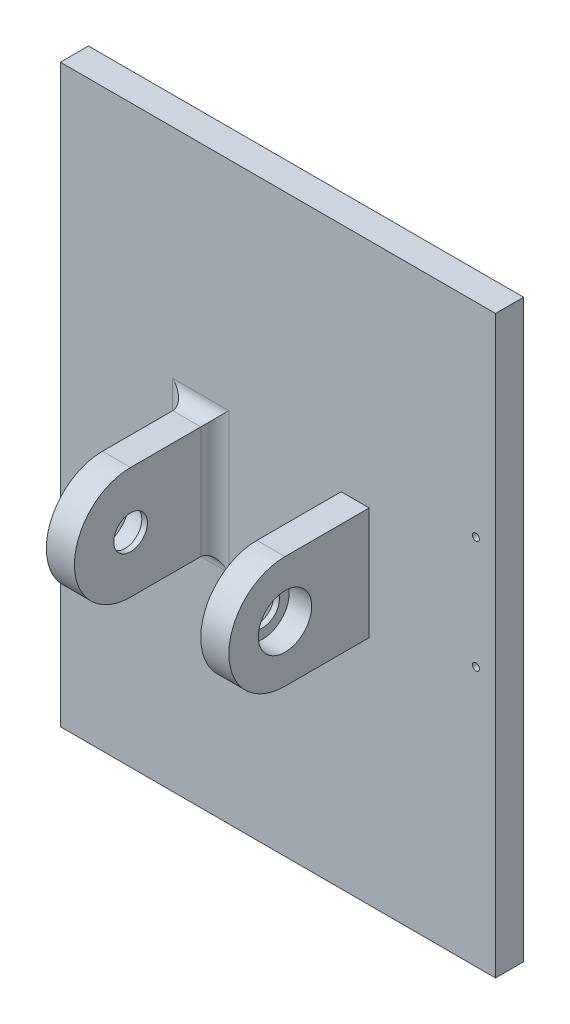
SolidWorks part; units mm, degrees
ref_plane "正面" through (0, 0, 0) normal (0, 0, 1) x (1, 0, 0)
ref_plane "平面" through (0, 0, 0) normal (0, 1, 0) x (1, 0, 0)
ref_plane "右側面" through (0, 0, 0) normal (1, 0, 0) x (0, 0, -1)
sketch "ｽｹｯﾁ2" plane through (0, 0, 0) normal (0, 0, 1) x (1, 0, 0)
  line L1 (-77.5, 102.5) -> (77.5, 102.5)
  line L2 (-77.5, 102.5) -> (-77.5, -102.5)
  line L3 (-77.5, -102.5) -> (77.5, -102.5)
  line L4 (77.5, 102.5) -> (77.5, -102.5)
  line L5 (-77.5, 102.5) -> (77.5, -102.5) construction
  line L6 (-77.5, -102.5) -> (77.5, 102.5) construction
  point P0 (0, 0)
  dimension "D1" = 155
  dimension "D2" = 205
extrude "ﾎﾞｽ - 押し出し1" add sketch "ｽｹｯﾁ2" along normal blind 10
sketch "ｽｹｯﾁ3" plane through (0, 0, 0) normal (0, 0, 1) x (1, 0, 0)
  line L0 (-32.5, 20) -> (-32.5, -20)
  line L1 (-32.5, -20) -> (-22.5, -20)
  line L2 (-22.5, -20) -> (-22.5, 20)
  line L3 (-22.5, 20) -> (-32.5, 20)
  dimension "D1" = 10
  dimension "D2" = 20
  dimension "D3" = 20
  dimension "D4" = 22.5
extrude "ﾎﾞｽ - 押し出し2" add sketch "ｽｹｯﾁ3" along normal blind 40
ref_plane "平面1" through (-32.5, 0, 0) normal (-1, 0, 0) x (0, 0, 1)
sketch "ｽｹｯﾁ4" plane through (-32.5, 0, 0) normal (-1, 0, 0) x (0, 0, 1)
  line L0 (40, 20) -> (40, -20) construction
  circle A0 centre (40, 0) radius 20
extrude "ﾎﾞｽ - 押し出し3" add sketch "ｽｹｯﾁ4" against normal blind 10
sketch "ｽｹｯﾁ5" plane through (-32.5, 0, 0) normal (-1, 0, 0) x (0, 0, 1)
  circle A0 centre (40, 0) radius 9.5
  dimension "D1" = 19
extrude "ｶｯﾄ - 押し出し1" cut sketch "ｽｹｯﾁ5" against normal blind 8
sketch "ｽｹｯﾁ13" plane through (-22.5, 0, 0) normal (1, 0, 0) x (0, 0, -1)
  circle A0 centre (-40, 0) radius 6
  dimension "D1" = 12
extrude "ｶｯﾄ - 押し出し2" cut sketch "ｽｹｯﾁ13" against normal through all
hole_wizard "M3x0.5 ねじ穴2" positions "ｽｹｯﾁ10" profile "ｽｹｯﾁ11" tap size "M3x0.5" standard "JIS" end condition through all
sketch "ｽｹｯﾁ10" plane through (0, 0, 10) normal (0, 0, 1) x (1, 0, 0)
  point P0 (70.5, -10.0009)
  point P3 (70.5, 29.9991)
sketch "ｽｹｯﾁ11" plane through (70.5, -10.0009, 10) normal (1, 0, 0) x (0, -1, 0)
  line L0 (0, 0) -> (0, 10)
  line L1 (0, 10) -> (1.25, 10)
  line L2 (1.25, 10) -> (1.25, 0)
  line L5 (1.25, 0) -> (0, 0)
  line L11 (0, -6.35) -> (0, 107.95) construction
  dimension "次ｻｰﾌｪｽまでのねじ下穴ﾄﾞﾘﾙ直径" = 2.5
  dimension "次ｻｰﾌｪｽまでのねじ下穴ﾄﾞﾘﾙの深さ" = 10
cosmetic thread "穴のねじ山4" parameters "D2"=3
cosmetic thread "穴のねじ山5" parameters "D2"=3
mirror "ﾐﾗｰ2" about plane through (0, 0, 0) normal (1, 0, 0) of "ｶｯﾄ - 押し出し2", "ｶｯﾄ - 押し出し1", "ﾎﾞｽ - 押し出し3", "ﾎﾞｽ - 押し出し2"
ref_plane "平面2" through (-22.5, 0, 0) normal (1, 0, 0) x (0, 0, -1)
fillet "ﾌｨﾚｯﾄ1" radius 5 4 edges at (-27.5, -20, 10) (-32.5, 0, 10) (-27.5, 20, 10) (-22.5, 0, 10)
